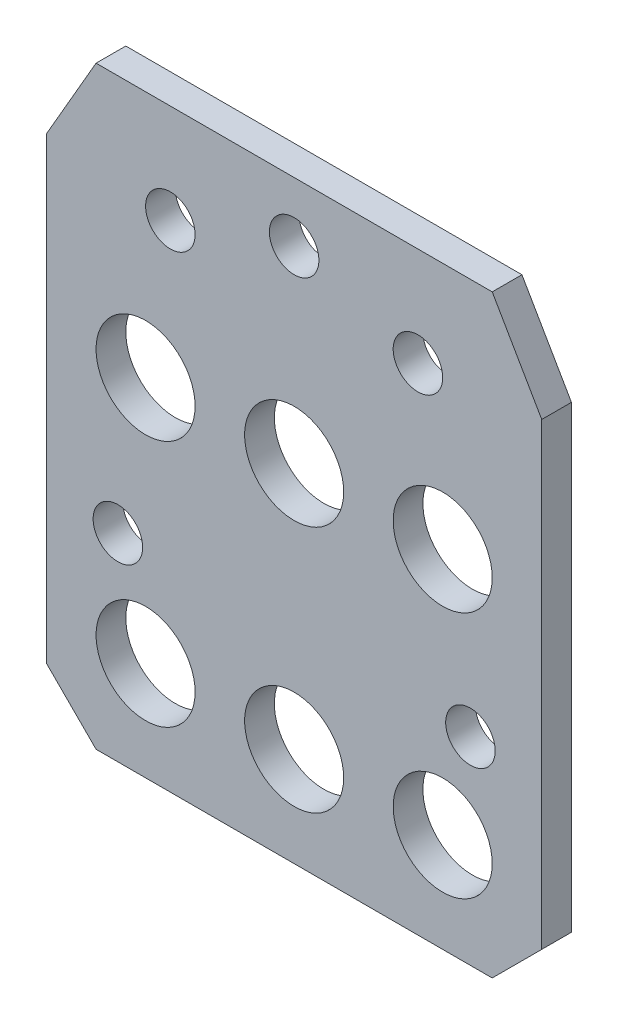
SolidWorks part; units mm, degrees
material "Q235"
ref_plane "前视基准面" through (0, 0, 0) normal (0, 0, 1) x (1, 0, 0)
ref_plane "上视基准面" through (0, 0, 0) normal (0, 1, 0) x (1, 0, 0)
ref_plane "右视基准面" through (0, 0, 0) normal (1, 0, 0) x (0, 0, -1)
sketch "草图1" plane through (0, 0, 0) normal (0, 0, 1) x (1, 0, 0)
  line L0 (-20, -30) -> (-20, 30) construction
  line L1 (20, -30) -> (14.2842, -30)
  line L2 (14.2842, -30) -> (14.2842, -35) construction
  line L3 (-20, -30) -> (-14.2842, -30)
  line L4 (-20, -30) -> (-20, -35) construction
  line L5 (-20, 30) -> (20, 30)
  line L6 (20, 30) -> (20, -30) construction
  line L7 (14.2842, -35) -> (-14.2842, -35) construction
  line L8 (-20, -30) -> (-25, -25)
  line L9 (-25, -25) -> (-25, 21.3397)
  line L10 (-25, 21.3397) -> (-20, 30)
  line L11 (-14.2842, -30) -> (-14.2842, -35) construction
  line L12 (-20, -35) -> (-14.2842, -35) construction
  line L13 (14.2842, -35) -> (20, -35) construction
  line L14 (20, -30) -> (20, -35) construction
  line L15 (0, -35) -> (0, 30) construction
  line L16 (20, -30) -> (25, -25)
  line L17 (25, 21.3397) -> (20, 30)
  line L18 (25, -25) -> (25, 21.3397)
  line L19 (-14.2842, -30) -> (14.2842, -30)
  dimension "D1" = 40
  dimension "D2" = 5
  dimension "D3" = 30
  dimension "D4" = 45
  dimension "D5" = 60
  dimension "D6" = 30
  dimension "D7" = 5
base flange "基体-法兰1" sketch "草图1" thickness 3 reverse thickness direction no parameters "D1"=0.7366
sketch "草图6" plane through (0, 0, 0) normal (0, 0, 1) x (1, 0, 0)
  line L0 (0, 48.7443) -> (0, -31.2557) construction
  line L1 (20, 30) -> (-20, 30) construction
  line L2 (-17.8, -10) -> (17.8, -10) construction
  line L3 (-12.5, 20) -> (12.5, 20) construction
  circle A0 centre (0, 24) radius 2.5
  circle A1 centre (-17.8, -10) radius 2.5
  circle A2 centre (17.8, -10) radius 2.5
  circle A3 centre (-12.5, 20) radius 2.5
  circle A4 centre (12.5, 20) radius 2.5
  dimension "D1" = 5
  dimension "D3" = 5
  dimension "D4" = 5
  dimension "D7" = 17.8
  dimension "D2" = 6
  dimension "D5" = 35.6
  dimension "D6" = 40
  dimension "D9" = 25
  dimension "D10" = 10
  dimension "D11" = 12.5
extrude "切除-拉伸1" cut sketch "草图6" against normal up to next normal cut yes
sketch "草图7" plane through (0, 0, 0) normal (0, 0, 1) x (1, 0, 0)
  line L0 (-15, 5) -> (15, 5) construction
  line L1 (0, 0) -> (0, 15.0567) construction
  line L2 (20, 30) -> (-20, 30) construction
  line L4 (-20, -30) -> (20, -30) construction
  line L5 (-15, -20) -> (15, -20) construction
  circle A0 centre (-15, 5) radius 5
  circle A1 centre (15, 5) radius 5
  circle A2 centre (0, -20) radius 5
  circle A3 centre (-15, -20) radius 5
  circle A4 centre (15, -20) radius 5
  circle A5 centre (0, 5) radius 5
  dimension "D1" = 10
  dimension "D2" = 30
  dimension "D4" = 10
  dimension "D5" = 15
  dimension "D3" = 25
extrude "切除-拉伸2" cut sketch "草图7" against normal up to next normal cut yes
sketch "折弯-线1" plane through (0, 0, 0) normal (0, 1, 0) x (1, 0, 0)
sketch "边界框1" plane through (0, 0, 0) normal (0, 1, 0) x (1, 0, 0)
sheet metal parameters "钣金(11)" thickness 3 parameters "D1"=0.7366
flat pattern "平板型式(11)" [suppressed]
sketch "折弯-线2" plane through (0, 0, 0) normal (0, 1, 0) x (1, 0, 0)
sketch "边界框2" [suppressed] plane through (0, 0, 0) normal (0, 1, 0) x (1, 0, 0)
sheet metal parameters "钣金(12)" thickness 3 parameters "D1"=0.7366
flat pattern "平板型式(11)"
sketch "折弯-线3" plane through (0, 0, 0) normal (0, 1, 0) x (1, 0, 0)
sketch "边界框3" [suppressed] plane through (0, 0, 0) normal (0, 1, 0) x (1, 0, 0)
sheet metal parameters "钣金(13)" thickness 3 parameters "D1"=0.7366
flat pattern "平板型式(11)"
sketch "折弯-线4" plane through (0, 0, 0) normal (0, 1, 0) x (1, 0, 0)
sketch "边界框4" [suppressed] plane through (0, 0, 0) normal (0, 1, 0) x (1, 0, 0)
